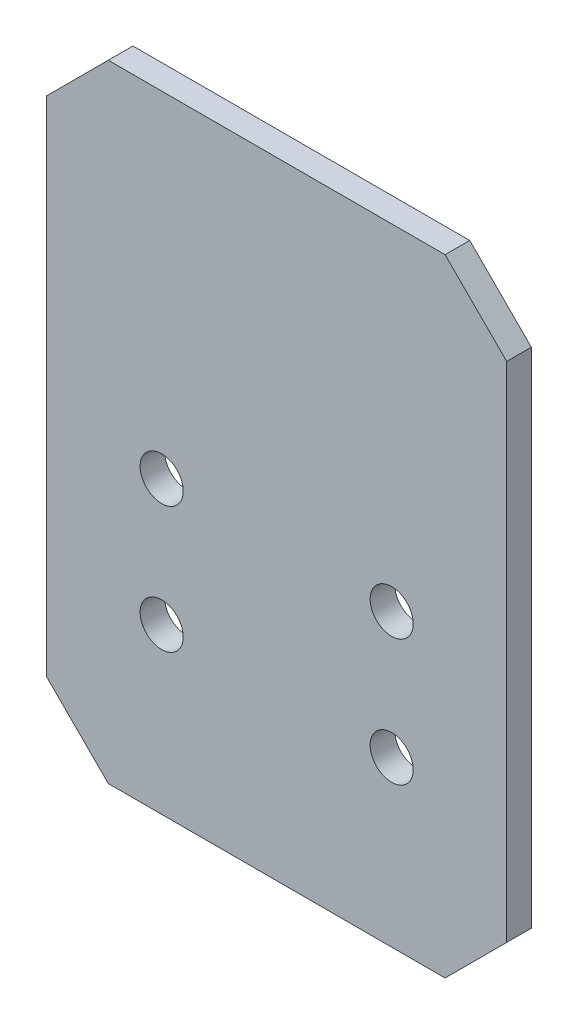
SolidWorks part; units mm, degrees
material "AISI 1020"
ref_plane "Спереди" through (0, 0, 0) normal (0, 0, 1) x (1, 0, 0)
ref_plane "Сверху" through (0, 0, 0) normal (0, 1, 0) x (1, 0, 0)
ref_plane "Справа" through (0, 0, 0) normal (1, 0, 0) x (0, 0, -1)
sketch "Эскиз1" plane through (0, 0, 0) normal (0, 0, 1) x (1, 0, 0)
  line L0 (-41, -132.5) -> (-56, -117.5) construction
  line L1 (56, -117.5) -> (41, -132.5) construction
  line L2 (41, -132.5) -> (-41, -132.5) construction
  line L3 (-41, -132.5) -> (-56, -117.5)
  line L4 (56, -117.5) -> (41, -132.5)
  line L5 (41, -132.5) -> (-41, -132.5)
  line L6 (56, -117.5) -> (56, 5)
  line L7 (56, 5) -> (41, 20)
  line L8 (41, 20) -> (-41, 20)
  line L9 (-41, 20) -> (-56, 5)
  line L10 (-56, 5) -> (-56, -117.5)
  line L11 (-41, -21.7262) -> (41, -21.7262) construction
  line L12 (41, -21.7262) -> (56, -36.7262) construction
  line L13 (-56, -36.7262) -> (-41, -21.7262) construction
  line L14 (56, 5) -> (15, 5) construction
  circle A0 centre (28, -61.7262) radius 5.25 construction
  circle A1 centre (28, -92.5) radius 5.25 construction
  circle A2 centre (-28, -92.5) radius 5.25 construction
  circle A3 centre (-28, -61.7262) radius 5.25 construction
  circle A4 centre (28, -61.7262) radius 5.25
  circle A5 centre (28, -92.5) radius 5.25
  circle A6 centre (-28, -92.5) radius 5.25
  circle A7 centre (-28, -61.7262) radius 5.25
base flange "Базовая кромка1" sketch "Эскиз1" thickness 6 reverse thickness direction no parameters "D1"=0.75
sketch "Сгиб-Линии1" [suppressed] plane through (0, 0, 0) normal (0, 1, 0) x (1, 0, 0)
sketch "Граничная рамка1" [suppressed] plane through (0, 0, 0) normal (0, 1, 0) x (1, 0, 0)
sheet metal parameters "Листовой металл3" thickness 6 parameters "D1"=0.75
flat pattern "Развертка3" [suppressed]
sketch "Сгиб-Линии2" plane through (0, 0, 0) normal (0, 1, 0) x (1, 0, 0)
sketch3d "Граничная рамка2" [suppressed]
  line L0 (56, 20, 0) -> (56, -132.5, 0) construction
  line L1 (-56, 20, 0) -> (-56, -132.5, 0) construction
  line L2 (56, 20, 0) -> (-56, 20, 0) construction
  line L3 (56, -132.5, 0) -> (-56, -132.5, 0) construction
